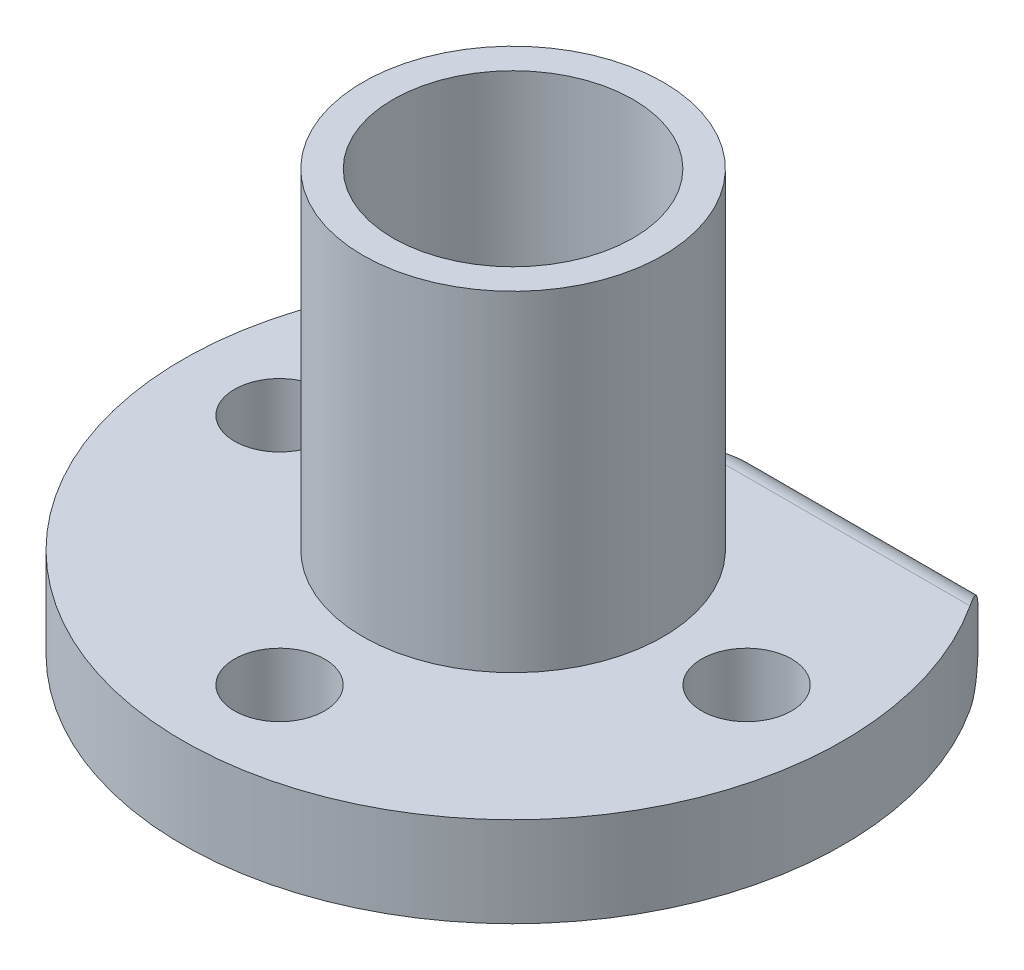
SolidWorks part; units mm, degrees
ref_plane "Front" through (0, 0, 0) normal (0, 0, 1) x (1, 0, 0)
ref_plane "Top" through (0, 0, 0) normal (0, 1, 0) x (1, 0, 0)
ref_plane "Right" through (0, 0, 0) normal (1, 0, 0) x (0, 0, -1)
sketch "Esquisse1" plane through (0, 0, 0) normal (0, 0, 1) x (1, 0, 0)
  line L0 (0, 0) -> (0, 18.0588) construction
  line L1 (4, 0) -> (4, 15)
  line L2 (4, 15) -> (5, 15)
  line L3 (5, 15) -> (5, 4)
  line L4 (5, 4) -> (11, 4)
  line L5 (11, 4) -> (11, 1)
  line L6 (11, 1) -> (5, 1)
  line L7 (5, 1) -> (5, 0)
  line L8 (5, 0) -> (4, 0)
  dimension "D1" = 8
  dimension "D2" = 10
  dimension "D3" = 22
  dimension "D4" = 1
  dimension "D5" = 15
  dimension "D6" = 3
revolve "Révolution1" add sketch "Esquisse1" angle 360 about L0
sketch "Esquisse2" plane through (0, 1, 0) normal (0, -1, 0) x (1, 0, 0)
  line L0 (0, 0) -> (7.7782, 0) construction
  circle A0 centre (7.7782, 0) radius 1.5
  circle A1 centre (0, -7.7782) radius 1.5
  circle A2 centre (-7.7782, 0) radius 1.5
  circle A3 centre (0, 7.7782) radius 1.5
  point P13 (0, 0)
  dimension "D1" = 3
  dimension "D3" = 11
  dimension "D2" = 4
extrude "Enlèv. mat.-Extru.1" cut sketch "Esquisse2" against normal through all
sketch "Esquisse3" plane through (0, 4, 0) normal (0, 1, 0) x (1, 0, 0)
  line L0 (8.4853, 7) -> (-8.4853, 7)
  line L1 (8.4853, 7) -> (8.4853, 14.7745)
  line L2 (8.4853, 14.7745) -> (-8.4853, 14.7745)
  line L3 (-8.4853, 14.7745) -> (-8.4853, 7)
  circle A0 centre (0, 0) radius 11 construction
  dimension "D1" = 7
extrude "Enlèv. mat.-Extru.2" cut sketch "Esquisse3" against normal through all
fillet "Congé1" radius 1 2 edges at (-4.8838, 1, -7) (-4.8838, 4, -7)
